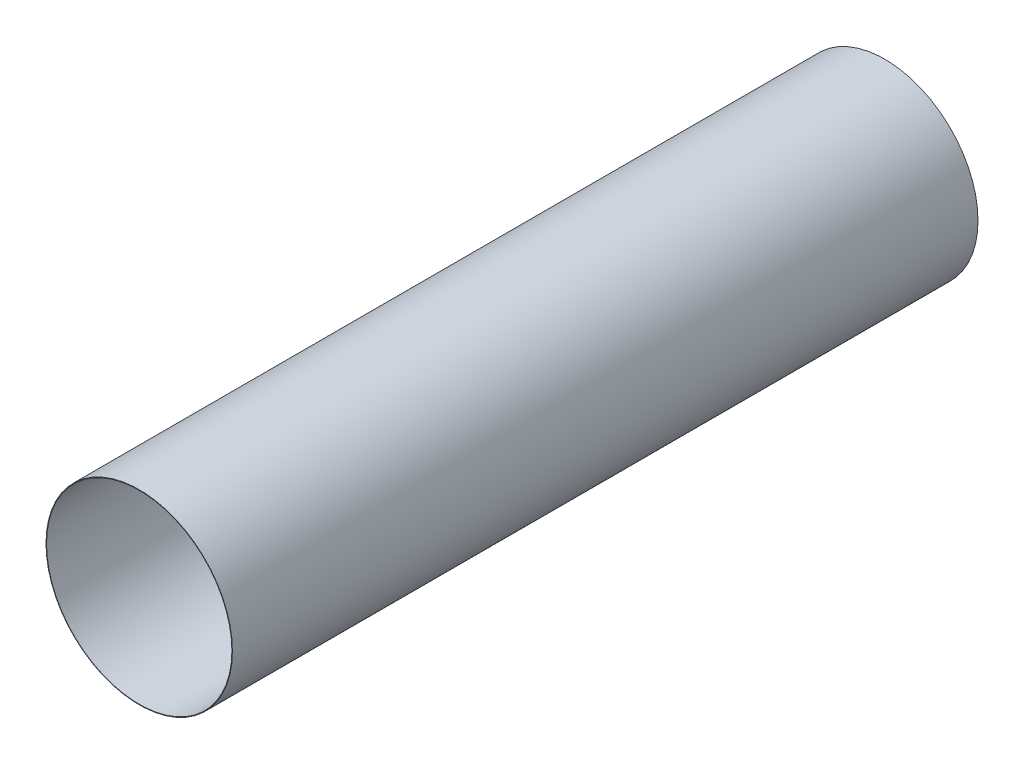
SolidWorks part; units mm, degrees
material "Plain Carbon Steel"
ref_plane "Front Plane" through (0, 0, 0) normal (0, 0, 1) x (1, 0, 0)
ref_plane "Top Plane" through (0, 0, 0) normal (0, 1, 0) x (1, 0, 0)
ref_plane "Right Plane" through (0, 0, 0) normal (1, 0, 0) x (0, 0, -1)
sketch "DuctSketch" plane through (0, 0, 0) normal (0, 0, 1) x (1, 0, 0)
  circle A0 centre (0, 0) radius 375
  circle A1 centre (0, 0) radius 373 construction
  dimension "InnerDiameter" = 746
  dimension "OuterDiameter" = 750
extrude "Extrusion" add sketch "DuctSketch" along normal blind 3000 thin thin type one direction reverse wall 2
sketch "FilterSketch" plane through (0, 0, 0) normal (0, 0, 1) x (1, 0, 0)
  circle A0 centre (0, 0) radius 375 construction
  dimension "NominalDiameter" = 750
